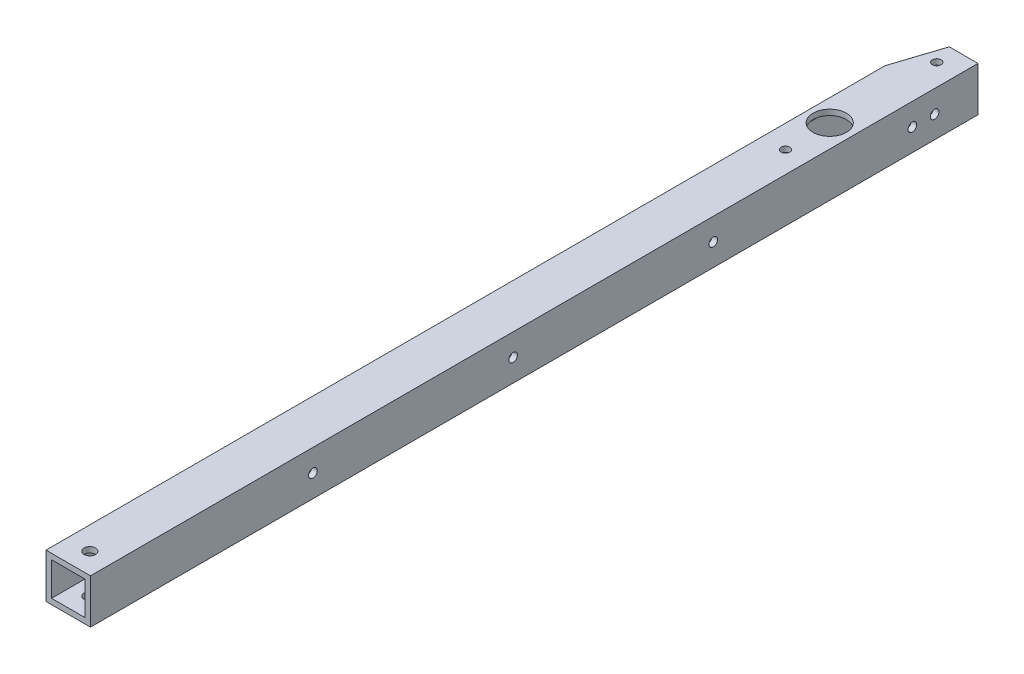
SolidWorks part; units mm, degrees
material "6061 Alloy"
ref_plane "Front Plane" through (0, 0, 0) normal (0, 0, 1) x (1, 0, 0)
ref_plane "Top Plane" through (0, 0, 0) normal (0, 1, 0) x (1, 0, 0)
ref_plane "Right Plane" through (0, 0, 0) normal (1, 0, 0) x (0, 0, -1)
sketch "Sketch1" plane through (0, 0, 0) normal (0, 0, 1) x (1, 0, 0)
  line L0 (-9.525, 9.525) -> (9.525, 9.525)
  line L2 (-12.7, 12.7) -> (12.7, 12.7)
  line L3 (-12.7, 12.7) -> (-12.7, -12.7)
  line L4 (-12.7, -12.7) -> (12.7, -12.7)
  line L5 (12.7, 12.7) -> (12.7, -12.7)
  line L10 (9.525, 9.525) -> (9.525, -9.525)
  line L11 (-9.525, -9.525) -> (9.525, -9.525)
  line L12 (-9.525, 9.525) -> (-9.525, -9.525)
  point P12 (0, 12.7)
  point P14 (12.7, 0)
  dimension "Wall Thickness" = 3.175
  dimension "Outside Width" = 25.4
  dimension "Outside Height" = 25.4
  dimension "Inside Height" = 19.05
  dimension "Inside Width" = 19.05
sketch "Sketch2" plane through (0, 0, 0) normal (1, 0, 0) x (0, 0, -1)
  line L0 (260.35, 0) -> (-260.35, 0)
  point P4 (0, 0)
  point P7 (-260.35, 0)
  point P10 (260.35, 0)
  dimension "Length" = 520.7
sketch "Sketch3" plane through (0, 0, 0) normal (0, 0, 1) x (1, 0, 0)
  line L21 (12.7, 12.7) -> (-12.7, 12.7)
  line L22 (12.7, -12.7) -> (12.7, 12.7)
  line L23 (-12.7, -12.7) -> (12.7, -12.7)
  line L24 (-12.7, 12.7) -> (-12.7, -12.7)
  line L25 (12.7, 12.7) -> (-12.7, 12.7)
  line L26 (12.7, -12.7) -> (12.7, 12.7)
  line L27 (-12.7, -12.7) -> (12.7, -12.7)
  line L28 (-12.7, 12.7) -> (-12.7, -12.7)
  line L29 (9.525, 9.525) -> (-9.525, 9.525)
  line L30 (9.525, -9.525) -> (9.525, 9.525)
  line L31 (-9.525, -9.525) -> (9.525, -9.525)
  line L32 (-9.525, 9.525) -> (-9.525, -9.525)
  line L33 (9.525, 9.525) -> (-9.525, 9.525)
  line L34 (9.525, -9.525) -> (9.525, 9.525)
  line L35 (-9.525, -9.525) -> (9.525, -9.525)
  line L36 (-9.525, 9.525) -> (-9.525, -9.525)
  dimension "D1" = 0
  dimension "D2" = 0
extrude "Boss-Extrude1" add sketch "Sketch3" along normal up to vertex (260.35 mm away) and the other way up to vertex (260.35 mm away) up to point (0, 0, 260.35) other way up to point (0, 0, -260.35)
sketch "Drawing Reference" plane through (0, 0, 0) normal (1, 0, 0) x (0, 0, -1)
  line L0 (-260.35, 0) -> (260.35, 0) construction
  line L1 (0, -12.7) -> (0, 12.7) construction
  line L2 (-260.35, -12.7) -> (260.35, -12.7) construction
  line L5 (-260.35, 12.7) -> (260.35, 12.7) construction
  point P7 (-242.062, 0)
  point P8 (242.062, 0)
  dimension "D1" = 18.288
sketch "Sketch4" plane through (0, 12.7, 0) normal (0, 1, 0) x (1, 0, 0)
  line L7 (-12.7, 218.6635) -> (-12.7, 260.35)
  line L10 (-12.7, -260.35) -> (-12.7, 260.35) construction
  line L11 (-12.7, 260.35) -> (12.7, 260.35)
  line L12 (12.7, 260.35) -> (12.7, 246.38)
  line L13 (12.7, -260.35) -> (12.7, 260.35) construction
  line L14 (12.7, 246.38) -> (-3.6932, 246.38)
  line L15 (-3.6932, 246.38) -> (-12.7, 218.6635)
  dimension "D1" = 13.97
  dimension "D2" = 41.6865
  dimension "D3" = 9.0068
extrude "Cut-Extrude1" cut sketch "Sketch4" against normal blind 25.4
sketch "Sketch5" plane through (0, 12.7, 0) normal (0, -1, 0) x (1, 0, 0)
  circle A0 centre (-0.2787, -174.7012) radius 9.525
extrude "Cut-Extrude2" cut sketch "Sketch5" along normal blind 3.175
sketch "Sketch6" plane through (12.7, 0, 0) normal (1, 0, 0) x (0, 0, -1)
  line L0 (246.38, 0) -> (208.915, 0) construction
  line L1 (246.38, -12.7) -> (246.38, 12.7) construction
  line L2 (208.915, 0) -> (227.965, 0) construction
  dimension "D1" = 37.465
hole_wizard "#10 Clearance Hole2" positions "Sketch9" profile "Sketch10" hole size "#10" standard "ANSI Inch" end condition through all
sketch "Sketch9" plane through (0, -12.7, 0) normal (0, -1, 0) x (-1, 0, 0)
  point P0 (-0.379, 148.7845)
  point P3 (-0.3824, 235.171)
sketch "Sketch10" plane through (0.379, -12.7, -148.7845) normal (1, 0, 0) x (0, 0, -1)
  line L0 (0, 0) -> (0, 25.4)
  line L1 (0, 25.4) -> (2.4892, 25.4)
  line L2 (2.4892, 25.4) -> (2.4892, 0)
  line L5 (2.4892, 0) -> (0, 0)
  line L11 (0, -6.35) -> (0, 107.95) construction
  dimension "Thru Hole Dia." = 4.9784
  dimension "Thru Hole Depth" = 25.4
sketch "Sketch15" plane through (0, -12.7, 0) normal (0, -1, 0) x (1, 0, 0)
  line L0 (0.3633, 248.3836) -> (0.3633, 260.35) construction
  line L1 (-12.7, 260.35) -> (12.7, 260.35) construction
  circle A0 centre (0.3633, 248.3836) radius 3.175 construction
  point P2 (0, 260.35)
  dimension "D1" = 11.9664
  dimension "D2" = 0.3633
hole_wizard "1/4 Clearance Hole1" positions "Sketch11" profile "Sketch12" hole size "1/4" standard "ANSI Inch" end condition through all
sketch "Sketch11" plane through (0, -12.7, 0) normal (0, -1, 0) x (-1, 0, 0)
  point P0 (-0.3633, -248.3836)
sketch "Sketch12" plane through (0.3633, -12.7, 248.3836) normal (1, 0, 0) x (0, 0, -1)
  line L0 (0, 0) -> (0, 25.4)
  line L1 (0, 25.4) -> (3.2639, 25.4)
  line L2 (3.2639, 25.4) -> (3.2639, 0)
  line L5 (3.2639, 0) -> (0, 0)
  line L11 (0, -6.35) -> (0, 107.95) construction
  dimension "Thru Hole Dia." = 6.5278
  dimension "Thru Hole Depth" = 25.4
hole_wizard "#10 Clearance Hole3" positions "Sketch13" profile "Sketch14" hole size "#10" standard "ANSI Inch"
sketch "Sketch13" plane through (12.7, 0, 0) normal (1, 0, 0) x (0, 0, -1)
  point P0 (221.6129, -0.0596)
  point P4 (208.915, 0)
sketch "Sketch14" plane through (12.7, -0.0596, -221.6129) normal (0, 1, 0) x (0, 0, -1)
  line L0 (0, 0) -> (0, 6.5757)
  line L1 (0, 6.5757) -> (2.4892, 5.08)
  line L2 (2.4892, 5.08) -> (2.4892, 0)
  line L5 (2.4892, 0) -> (0, 0)
  line L10 (0, 6.5757) -> (-2.4892, 5.08) construction
  line L11 (0, -6.35) -> (0, 107.95) construction
  dimension "Hole Dia." = 4.9784
  dimension "Hole Depth" = 5.08
  dimension "Drill Angle" = 118
sketch "Sketch16" plane through (12.7, 0, 0) normal (1, 0, 0) x (0, 0, -1)
  line L0 (-260.35, 0) -> (-133.35, 0) construction
  line L1 (-260.35, -12.7) -> (-260.35, 12.7) construction
  line L2 (-133.35, 0) -> (-19.05, 0) construction
  line L3 (-19.05, 0) -> (95.25, 0) construction
  dimension "D1" = 127
  dimension "D2" = 114.3
  dimension "D3" = 114.3
hole_wizard "#10 Clearance Hole4" positions "Sketch17" profile "Sketch18" hole size "#10" standard "ANSI Inch" end condition through all
sketch "Sketch17" plane through (12.7, 0, 0) normal (1, 0, 0) x (0, 0, -1)
  point P0 (-133.35, 0)
  point P3 (-19.05, 0)
  point P6 (95.25, 0)
sketch "Sketch18" plane through (12.7, 0, 133.35) normal (0, 1, 0) x (0, 0, -1)
  line L0 (0, 0) -> (0, 25.4)
  line L1 (0, 25.4) -> (2.4892, 25.4)
  line L2 (2.4892, 25.4) -> (2.4892, 0)
  line L5 (2.4892, 0) -> (0, 0)
  line L11 (0, -6.35) -> (0, 107.95) construction
  dimension "Thru Hole Dia." = 4.9784
  dimension "Thru Hole Depth" = 25.4
sketch "Sketch19" plane through (-12.7, 0, 0) normal (-1, 0, 0) x (0, 0, 1)
  line L0 (260.35, 0) -> (228.6, 0) construction
  line L1 (260.35, 12.7) -> (260.35, -12.7) construction
  line L2 (228.6, 0) -> (101.6, 0) construction
  dimension "D1" = 31.75
  dimension "D2" = 127
hole_wizard "1/4 (0.25) Diameter Hole1" positions "Sketch20" profile "Sketch21" hole size "1/4" standard "ANSI Inch"
sketch "Sketch20" plane through (-12.7, 0, 0) normal (-1, 0, 0) x (0, 0, 1)
  point P0 (101.6, 0)
  point P3 (228.6, 0)
sketch "Sketch21" plane through (-12.7, 0, 101.6) normal (0, 1, 0) x (0, 0, 1)
  line L0 (0, 0) -> (0, 6.9877)
  line L1 (0, 6.9877) -> (3.175, 5.08)
  line L2 (3.175, 5.08) -> (3.175, 0)
  line L5 (3.175, 0) -> (0, 0)
  line L10 (0, 6.9877) -> (-3.175, 5.08) construction
  line L11 (0, -6.35) -> (0, 107.95) construction
  dimension "Hole Dia." = 6.35
  dimension "Hole Depth" = 5.08
  dimension "Drill Angle" = 118
equation "\"D1@Drawing Reference\"=\"Outside Width@Sketch1\" * 0.72"
